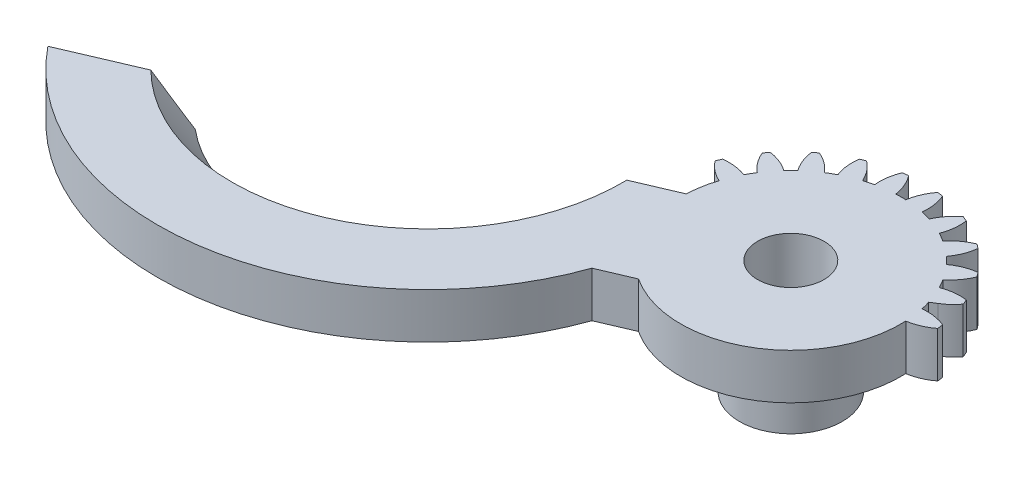
SolidWorks part; units mm, degrees
ref_plane "Front Plane" through (0, 0, 0) normal (0, 0, 1) x (1, 0, 0)
ref_plane "Top Plane" through (0, 0, 0) normal (0, 1, 0) x (1, 0, 0)
ref_plane "Right Plane" through (0, 0, 0) normal (1, 0, 0) x (0, 0, -1)
ref_plane "Plane1" through (0, 4, 0) normal (0, 1, 0) x (1, 0, 0)
sketch "Sketch1" plane through (0, 4, 0) normal (0, 1, 0) x (1, 0, 0)
  line L0 (1.4381, 3.6001) -> (2.0816, 4)
  arc A0 (-20.8986, -5.4553) -> (-21.9429, 2.4762) centre (-10.1063, 0) cw
  arc A1 (4.3495, 2.2179) -> (1.7031, 2.6025) centre (2.274, -2.7673) ccw
  arc A2 (1.7031, 2.6025) -> (1.4381, 3.6001) centre (-10.1063, 0) ccw
  arc A3 (2.0816, 4) -> (3.5217, 5.3071) centre (-0.7683, 8.5867) ccw
  arc A4 (3.5217, 5.3071) -> (3.2829, 5.8838) centre (-10.1063, 0) ccw
  arc A5 (3.2829, 5.8838) -> (0.6271, 5.5703) centre (2.5684, 0.5313) ccw
  arc A6 (0.6271, 5.5703) -> (0.0844, 6.5103) centre (-10.1063, 0) ccw
  arc A7 (0.0844, 6.5103) -> (1.6838, 8.6535) centre (-3.3089, 10.711) ccw
  arc A8 (1.6838, 8.6535) -> (1.3038, 9.1487) centre (-10.1063, 0) ccw
  arc A9 (1.3038, 9.1487) -> (-1.1803, 8.1585) centre (1.999, 3.7936) ccw
  arc A10 (-1.1803, 8.1585) -> (-1.9479, 8.926) centre (-10.1063, 0) ccw
  arc A11 (-1.9479, 8.926) -> (-0.9576, 11.4102) centre (-6.3127, 12.1053) ccw
  arc A12 (-0.9576, 11.4102) -> (-1.4528, 11.7901) centre (-10.1063, 0) ccw
  arc A13 (-1.4528, 11.7901) -> (-3.596, 10.1907) centre (0.6046, 6.7975) ccw
  arc A14 (-3.596, 10.1907) -> (-4.5361, 10.7334) centre (-10.1063, 0) ccw
  arc A15 (-4.5361, 10.7334) -> (-4.2225, 13.3892) centre (-9.5751, 12.6747) ccw
  arc A16 (-4.2225, 13.3892) -> (-4.7992, 13.6281) centre (-10.1063, 0) ccw
  arc A17 (-4.7992, 13.6281) -> (-6.4554, 11.5285) centre (-1.5196, 9.3381) ccw
  arc A18 (-6.4554, 11.5285) -> (-7.5039, 11.8094) centre (-10.1063, 0) ccw
  arc A19 (-7.5039, 11.8094) -> (-7.8884, 14.4558) centre (-12.8736, 12.3803) ccw
  arc A20 (-7.8884, 14.4558) -> (-8.5072, 14.5373) centre (-10.1063, 0) ccw
  arc A21 (-8.5072, 14.5373) -> (-9.5636, 12.0806) centre (-4.2291, 11.2423) ccw
  arc A22 (-9.5636, 12.0806) -> (-10.6491, 12.0806) centre (-10.1063, 0) ccw
  arc A23 (-10.6491, 12.0806) -> (-11.7054, 14.5373) centre (-15.9836, 11.2423) ccw
  arc A24 (-11.7054, 14.5373) -> (-12.3243, 14.4558) centre (-10.1063, 0) ccw
  arc A25 (-12.3243, 14.4558) -> (-12.7088, 11.8094) centre (-7.3391, 12.3803) ccw
  arc A26 (-12.7088, 11.8094) -> (-13.7573, 11.5285) centre (-10.1063, 0) ccw
  arc A27 (-13.7573, 11.5285) -> (-15.4135, 13.6281) centre (-18.6931, 9.3381) ccw
  arc A28 (-15.4135, 13.6281) -> (-15.9901, 13.3892) centre (-10.1063, 0) ccw
  arc A29 (-15.9901, 13.3892) -> (-15.6766, 10.7334) centre (-10.6376, 12.6747) ccw
  arc A30 (-15.6766, 10.7334) -> (-16.6166, 10.1907) centre (-10.1063, 0) ccw
  arc A31 (-16.6166, 10.1907) -> (-18.7599, 11.7901) centre (-20.8173, 6.7975) ccw
  arc A32 (-18.7599, 11.7901) -> (-19.255, 11.4102) centre (-10.1063, 0) ccw
  arc A33 (-19.255, 11.4102) -> (-18.2648, 8.926) centre (-13.9, 12.1053) ccw
  arc A34 (-18.2648, 8.926) -> (-19.0324, 8.1585) centre (-10.1063, 0) ccw
  arc A35 (-19.0324, 8.1585) -> (-21.5165, 9.1487) centre (-22.2117, 3.7936) ccw
  arc A36 (-21.5165, 9.1487) -> (-21.8965, 8.6535) centre (-10.1063, 0) ccw
  arc A37 (-21.8965, 8.6535) -> (-20.2971, 6.5103) centre (-16.9038, 10.711) ccw
  arc A38 (-20.2971, 6.5103) -> (-20.8398, 5.5703) centre (-10.1063, 0) ccw
  arc A39 (-20.8398, 5.5703) -> (-23.4956, 5.8838) centre (-22.7811, 0.5313) ccw
  arc A40 (-23.4956, 5.8838) -> (-23.7344, 5.3071) centre (-10.1063, 0) ccw
  arc A41 (-23.7344, 5.3071) -> (-21.6348, 3.6509) centre (-19.4444, 8.5867) ccw
  arc A42 (-21.6348, 3.6509) -> (-21.9429, 2.4762) centre (-10.1063, 0) ccw
  arc A44 (-20.8986, -5.4553) -> (1.9742, 0.5427) centre (-10.1063, 0) ccw
  arc A45 (1.9742, 0.5427) -> (4.431, 1.5991) centre (1.1359, 5.8773) ccw
  arc A46 (4.431, 1.5991) -> (4.3495, 2.2179) centre (-10.1063, 0) ccw
  circle A47 centre (-10.1063, 0) radius 3.65
  dimension "D5" = 5.4
  dimension "D6" = 12.0927
  dimension "D7" = 5.4
  dimension "D8" = 14.625
  dimension "D9" = 5.4
  dimension "D10" = 0.0844
  dimension "D11" = 5.4
  dimension "D12" = 0.6046
  dimension "D13" = 5.4
  dimension "D14" = 0.6271
  dimension "D15" = 5.4
  dimension "D16" = 1.1359
  dimension "D17" = 5.4
  dimension "D18" = 1.3038
  dimension "D19" = 5.4
  dimension "D20" = 1.4381
  dimension "D21" = 5.4
  dimension "D22" = 1.6838
  dimension "D23" = 5.4
  dimension "D24" = 1.7031
  dimension "D25" = 5.4
  dimension "D26" = 1.9742
  dimension "D27" = 5.4
  dimension "D28" = 1.999
  dimension "D29" = 5.4
  dimension "D30" = 2.0816
  dimension "D31" = 5.4
  dimension "D32" = 2.274
  dimension "D33" = 5.4
  dimension "D34" = 2.5684
  dimension "D35" = 5.4
  dimension "D36" = 3.2829
  dimension "D37" = 5.4
  dimension "D38" = 3.5217
  dimension "D39" = 5.4
  dimension "D40" = 0.9576
  dimension "D41" = 5.4
  dimension "D42" = 1.4528
  dimension "D43" = 5.4
  dimension "D44" = 1.5196
  dimension "D45" = 5.4
  dimension "D46" = 1.9479
  dimension "D48" = 4.2225
  dimension "D49" = 5.4
  dimension "D50" = 4.2291
  dimension "D53" = 7.3
  dimension "D51" = 4.5361
  dimension "D52" = 4.7992
  dimension "D54" = 7.3391
  dimension "D55" = 7.5039
  dimension "D56" = 7.8884
  dimension "D57" = 8.5072
  dimension "D58" = 10.6376
  dimension "D59" = 10.6491
  dimension "D60" = 11.7054
  dimension "D61" = 12.3243
  dimension "D62" = 13.7573
  dimension "D63" = 13.9
  dimension "D65" = 15.4135
  dimension "D66" = 15.6766
  dimension "D67" = 16.6166
  dimension "D68" = 16.9038
  dimension "D69" = 18.2648
  dimension "D70" = 18.7599
  dimension "D71" = 19.0324
  dimension "D72" = 19.4444
  dimension "D73" = 20.2971
  dimension "D74" = 20.8398
  dimension "D75" = 20.8986
  dimension "D76" = 21.5165
  dimension "D77" = 21.6348
  dimension "D78" = 21.9429
  dimension "D79" = 22.7811
  dimension "D82" = 0.5313
extrude "Boss-Extrude1" add sketch "Sketch1" against normal blind 5
sketch "草图1" plane through (0, -1, 0) normal (0, -1, 0) x (1, 0, 0)
  circle A0 centre (-10.1063, 0) radius 3.65
  circle A1 centre (-10.1063, 0) radius 5.65
  circle A2 centre (-10.1063, 0) radius 3.65 construction
  dimension "D1" = 2
extrude "凸台-拉伸1" add sketch "草图1" along normal blind 7.5
ref_axis "基准轴1" through (-10.1063, -8.5, 0) along (0, 1, 0)
ref_plane "基准面1" through (-6.3269, 0, -4.89) normal (0.7912, 0, 0.6115) x (0, 1, 0)
sketch "草图2" plane through (0, 4, 0) normal (0, 1, 0) x (1, 0, 0)
  line L0 (-12.9616, 13.3537) -> (-64.3454, -8.6376) construction
  line L2 (-10.5312, -0.5497) -> (-2.1227, 10.3297) construction
  line L3 (-20.2909, -11.6575) -> (-16.7151, -10.1271)
  line L4 (-22.1849, 0.5847) -> (-30.1689, -2.8323)
  line L5 (-59.9419, -15.5745) -> (-71.2839, -20.4287)
  line L6 (-16.7151, -10.1271) -> (-22.1849, 0.5847)
  arc A1 (-21.6348, 3.6509) -> (1.9742, 0.5427) centre (-10.1063, 0) ccw construction
  arc A2 (-30.1689, -2.8323) -> (-59.9419, -15.5745) centre (-48.2463, -1.7475) cw
  arc A3 (-20.2909, -11.6575) -> (-71.2839, -20.4287) centre (-48.2463, -1.7475) cw
  dimension "D4" = 38.14
  dimension "D5" = 18.11
  dimension "D6" = 29.66
  dimension "D1" = 29.13
  dimension "D2" = 13.4
  dimension "D3" = 8.11
  dimension "D7" = 12
extrude "凸台-拉伸2" add sketch "草图2" against normal up to surface (5 mm away) up to face at (-8.6998, -1, -8.7204)
ref_axis "基准轴2" through (-48.2463, -1, 1.7475) along (0, 1, 0)
ref_plane "基准面2" through (-18.2846, 0, -22.5485) normal (0.6298, 0, 0.7767) x (0.7767, 0, -0.6298)
sketch "草图3" plane through (-18.2846, 0, -22.5485) normal (0.6298, 0, 0.7767) x (0.7767, 0, -0.6298)
  line L0 (-60.0747, 4) -> (-56.2747, -1.2341)
  line L1 (-56.3677, 4) -> (-68.2347, 4) construction
  line L2 (-56.2747, -1.2341) -> (-56.2747, 4)
  line L3 (-25.2167, 4) -> (-56.3677, 4) construction
  line L4 (-56.2747, 4) -> (-60.0747, 4)
  line L5 (-38.5747, -1) -> (-38.5747, 4) construction
  point P9 (-56.0747, -4.6165)
  dimension "D1" = 54.02
  dimension "D2" = 17.7
  dimension "D3" = 3.8
revolve "切除-旋转1" cut sketch "草图3" angle 360 about axis through (-48.2463, -1, 1.7475) along (0, 1, 0)
